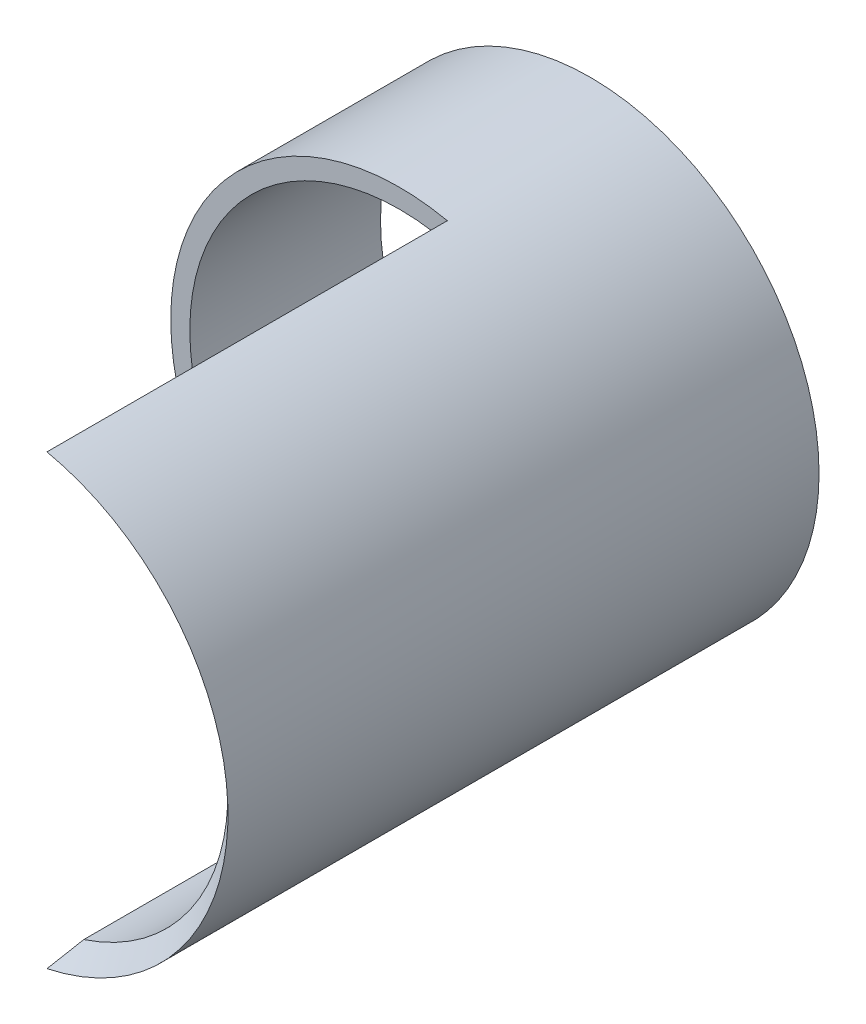
SolidWorks part; units mm, degrees
ref_plane "Plan de face" through (0, 0, 0) normal (0, 0, 1) x (1, 0, 0)
ref_plane "Plan de dessus" through (0, 0, 0) normal (0, 1, 0) x (1, 0, 0)
ref_plane "Plan de droite" through (0, 0, 0) normal (1, 0, 0) x (0, 0, -1)
sketch "Esquisse3" plane through (0, 0, 0) normal (0, 0, 1) x (1, 0, 0)
  circle A0 centre (0, 0) radius 24
extrude "Boss.-Extru.3" add sketch "Esquisse3" along normal blind 20
sketch "Esquisse4" plane through (0, 0, 0) normal (0, 0, -1) x (-1, 0, 0)
  circle A0 centre (0, 0) radius 22
extrude "Enlèv. mat.-Extru.6" cut sketch "Esquisse4" against normal blind 20
sketch "Esquisse5" plane through (0, 0, 20) normal (0, 0, 1) x (1, 0, 0)
  line L0 (0, -24) -> (0, -22)
  line L1 (0, 22) -> (0, 24)
  arc A0 (0, 24) -> (0, -24) centre (0, 0) cw
  circle A1 centre (0, 0) radius 24 construction
  arc A2 (0, 22) -> (0, -22) centre (0, 0) cw
  circle A3 centre (0, 0) radius 22 construction
extrude "Boss.-Extru.4" add sketch "Esquisse5" along normal blind 50
chamfer "Chanfrein1" distance 10 angle 45 1 edges at (22, 0, 70)
chamfer "Chanfrein2" distance 10 angle 45 1 edges at (0, 22, 40)
chamfer "Chanfrein3" distance 10 angle 45 1 edges at (0, -22, 40)
